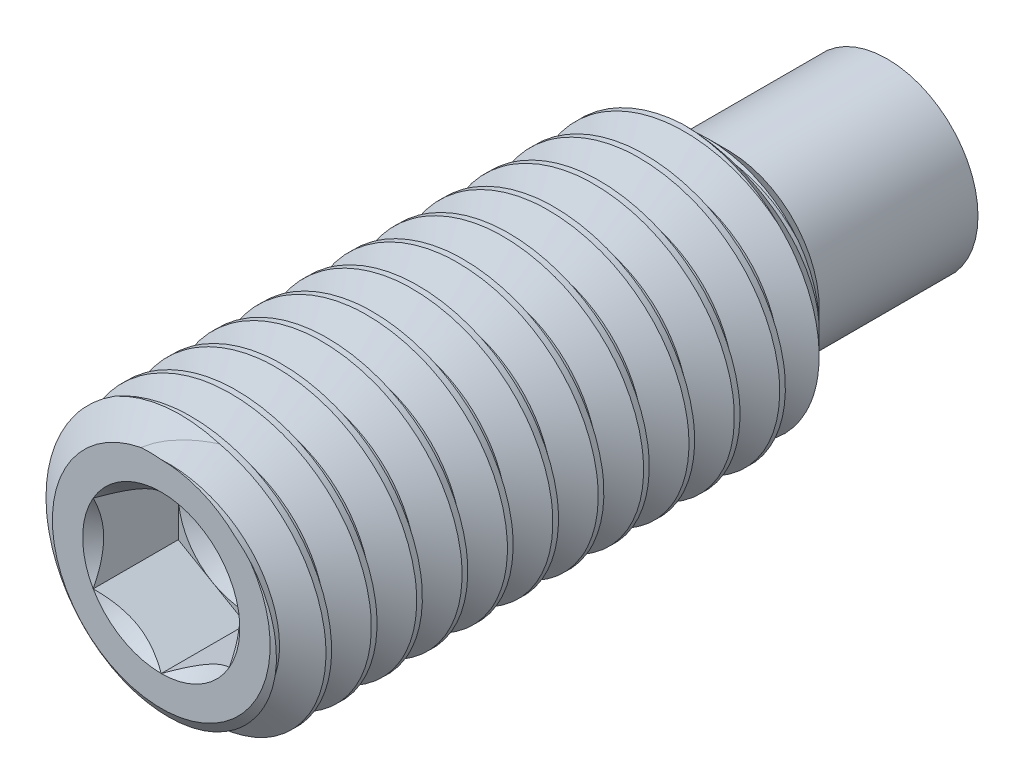
SolidWorks part; units mm, degrees
material "AISI 304"
ref_plane "Front" through (0, 0, 0) normal (0, 0, 1) x (1, 0, 0)
ref_plane "Top" through (0, 0, 0) normal (0, 1, 0) x (1, 0, 0)
ref_plane "Right" through (0, 0, 0) normal (1, 0, 0) x (0, 0, -1)
sketch "Sketch22" plane through (0, 0, 0) normal (1, 0, 0) x (0, 0, -1)
  line L0 (-4, 0) -> (-4, 1.2)
  line L1 (-4, 1.2) -> (-3.7899, 1.5)
  line L2 (-3.7899, 1.5) -> (1.75, 1.5)
  line L3 (1.75, 1.5) -> (2.25, 1)
  line L4 (-4, 1.2) -> (-4, -1.2) construction
  line L5 (4, 0) -> (-4, 0)
  line L6 (0, 1.5) -> (0, -1.5) construction
  line L8 (2.25, 1) -> (4, 1)
  line L9 (-2.77, -1.5) -> (2.77, -1.5) construction
  line L10 (4, 1) -> (4, 0)
  line L11 (4, 1) -> (4, -1) construction
  dimension "D3" = 35
  dimension "D1" = 45
  dimension "Dia" = 3
  dimension "D2" = 2.4
  dimension "A" = 2
  dimension "Length" = 8
  dimension "B" = 1.75
revolve "Revolve1" add sketch "Sketch22" angle 360 about L5
ref_plane "Plane1" through (0, 0, -2.25) normal (0, 0, 1) x (1, 0, 0)
sketch "Sketch27" plane through (0, 0, -2.25) normal (0, 0, 1) x (1, 0, 0)
  circle A0 centre (0, 0) radius 1.5 construction
  circle A1 centre (0, 0) radius 1.5
curve "Helix/Spiral1" pitch 0.5 height 8.5 radius 1.5 centre (0, 0, -2.25) axis (0, 0, 1) start towards (0, 1, 0)
sketch "Sketch28" plane through (0, 0, 0) normal (1, 0, 0) x (0, 0, -1)
  line L0 (2.25, 1.5) -> (2.6875, 1.5)
  line L1 (2.6875, 1.5) -> (2.5, 1.1752)
  line L2 (2.5, 1.1752) -> (2.4375, 1.1752)
  line L3 (2.4375, 1.1752) -> (2.25, 1.5)
  line L4 (2.3437, 1.3376) -> (2.5937, 1.3376) construction
  line L6 (-3.7899, 1.5) -> (1.75, 1.5) construction
  line L7 (2.25, 2.2462) -> (2.25, -2.2462) construction
  dimension "D1" = 0.0625
  dimension "D3" = 60
  dimension "D2" = 0.25
sweep "Cut-Sweep2" cut profiles "Sketch28" path "Helix/Spiral1" align with end faces yes
sketch "Sketch23" plane through (0, 0, 4) normal (0, 0, 1) x (1, 0, 0)
  line L1 (0, 0.866) -> (-0.75, 0.433)
  line L2 (-0.75, 0.433) -> (-0.75, -0.433)
  line L3 (-0.75, -0.433) -> (0, -0.866)
  line L4 (0, -0.866) -> (0.75, -0.433)
  line L5 (0.75, -0.433) -> (0.75, 0.433)
  line L6 (0.75, 0.433) -> (0, 0.866)
  circle A0 centre (0, 0) radius 0.75 construction
  dimension "Hex" = 1.5
extrude "Cut-Extrude10" cut sketch "Sketch23" against normal blind 0.9375
sketch "Sketch24" plane through (0, 0, 4) normal (0, 0, 1) x (1, 0, 0)
  circle A0 centre (0, 0) radius 0.866
extrude "Cut-Extrude11" cut sketch "Sketch24" against normal through all draft 45
sketch "Sketch26" plane through (0, 0, 3.0625) normal (0, 0, 1) x (1, 0, 0)
  circle A0 centre (0, 0) radius 0.75 construction
  circle A1 centre (0, 0) radius 0.75
extrude "Cut-Extrude12" cut sketch "Sketch26" against normal through all draft 60
sketch "Sketch30" plane through (0, 0, 0) normal (1, 0, 0) x (0, 0, -1)
  line L0 (-3.7899, 1.5) -> (1.75, 1.5) construction
  line L1 (-4, 0) -> (-4, 1.2) construction
  line L2 (2.25, 1.5) -> (2.25, -1.5) construction
  line L3 (-2.77, -1.5) -> (2.77, -1.5) construction
  point P0 (-4, 1.5)
  point P1 (4, 1.5)
  point P2 (4, -1.5)
  point P11 (0.5, -1.5)
  dimension "D1" = 1.75
equation "\"D1@Sketch28\" = \"D4@Helix/Spiral1\" * .125"
equation "\"D3@Helix/Spiral1\" = \"Length@Sketch22\" + \"D4@Helix/Spiral1\""
equation "\"D1@Sketch30\" = \"D4@Helix/Spiral1\" * 3.5"
equation "\"hex Depth@Cut-Extrude10\" = \"Hex@Sketch23\" * .625"
equation "\"D2@Sketch28\" = \"D4@Helix/Spiral1\" * .5"
equation "\"D2@Sketch22\" = \"Dia@Sketch22\" * .8"
